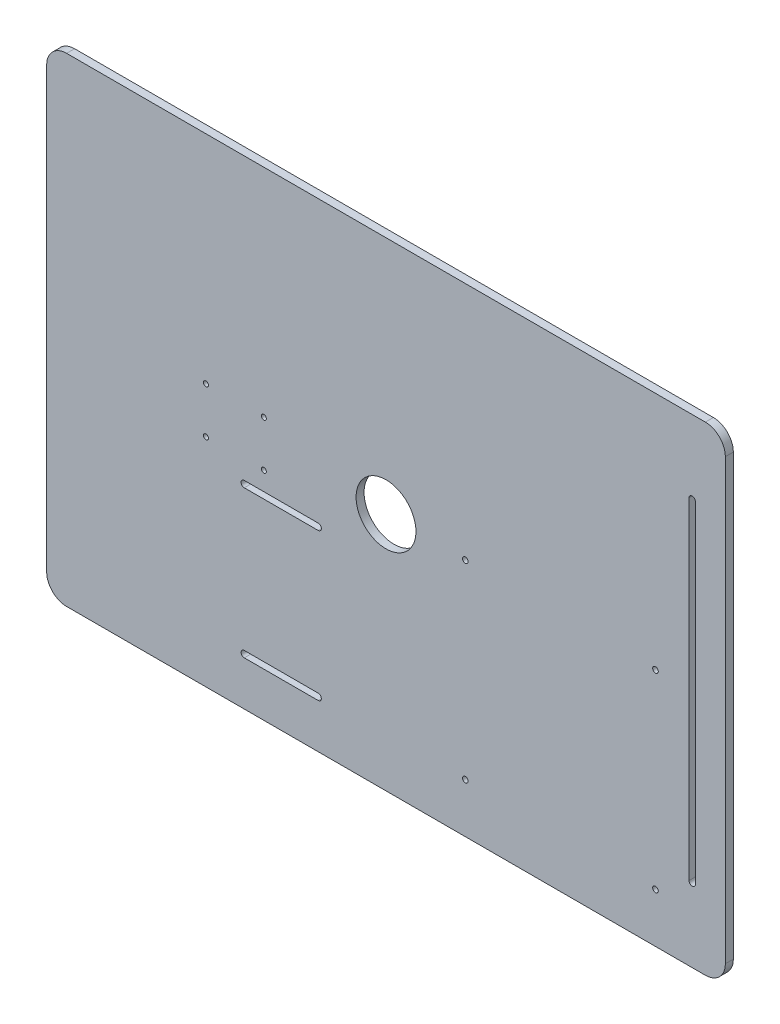
SolidWorks part; units mm, degrees
ref_plane "前视基准面" through (0, 0, 0) normal (0, 0, 1) x (1, 0, 0)
ref_plane "上视基准面" through (0, 0, 0) normal (0, 1, 0) x (1, 0, 0)
ref_plane "右视基准面" through (0, 0, 0) normal (1, 0, 0) x (0, 0, -1)
other "Configuration Table"
sketch "草图1" plane through (0, 0, 0) normal (0, 0, 1) x (1, 0, 0)
  line L0 (-232.03, 0) -> (-100.2513, 0) construction
  line L1 (160, -120) -> (-160, -120)
  line L2 (170, -110) -> (170, 110)
  line L3 (160, 120) -> (-160, 120)
  line L4 (-170, -110) -> (-170, 110)
  line L5 (170, -120) -> (-170, 120) construction
  line L6 (170, 120) -> (-170, -120) construction
  line L7 (0, -161.7122) -> (0, 250.7886) construction
  line L8 (0, 0) -> (270.6764, 0) construction
  line L9 (-110, 120) -> (-110, 83)
  line L10 (-170, 103) -> (-110, 103) construction
  line L11 (-110, 83) -> (-70, 83)
  line L12 (-70, 83) -> (-70, 120)
  line L17 (-100.2513, 0) -> (0, 0) construction
  line L18 (-76.2884, 0) -> (-76.2884, 20.8877) construction
  line L19 (-76.2884, 4.5) -> (-76.2884, -4.5) construction
  line L21 (39.75, 0) -> (135, 0)
  line L23 (151.8, -83) -> (151.8, 83)
  line L26 (155, 83) -> (155, -83)
  line L27 (-98.3572, 27.2299) -> (-98.3572, -46.7701)
  line L28 (98.3491, 27.2299) -> (-150.1076, 27.2299) construction
  line L30 (39.75, 0) -> (39.75, -95.25)
  circle A20 centre (-105, 115) radius 1.75
  circle A21 centre (-75, 115) radius 1.75
  circle A22 centre (-75, 91) radius 1.75
  circle A23 centre (-105, 91) radius 1.75
  circle A24 centre (-105, 115) radius 1.75
  circle A25 centre (-75, 115) radius 1.75
  circle A26 centre (-75, 91) radius 1.75
  circle A27 centre (-105, 91) radius 1.75
  circle A28 centre (-105.7503, -91) radius 1.75
  circle A29 centre (-75.7503, -91) radius 1.75
  circle A30 centre (-75.7503, -115) radius 1.75
  circle A31 centre (-105.7503, -115) radius 1.75
  circle A32 centre (105.7503, -115) radius 1.75
  circle A33 centre (105.7503, -91) radius 1.75
  circle A34 centre (75.7503, -115) radius 1.75
  circle A35 centre (75.7503, -91) radius 1.75
  circle A36 centre (105.7503, 91) radius 1.75
  circle A37 centre (75.7503, 91) radius 1.75
  circle A38 centre (75.7503, 115) radius 1.75
  circle A39 centre (105.7503, 115) radius 1.75
  circle A40 centre (-90.2053, 11.5) radius 1.25
  arc A43 (151.8, 83) -> (155, 83) centre (153.4, 83) cw
  arc A44 (151.8, -83) -> (155, -83) centre (153.4, -83) ccw
  circle A45 centre (0, 0) radius 15
  arc A46 (170, 110) -> (160, 120) centre (160, 110) ccw
  arc A47 (160, -120) -> (170, -110) centre (160, -110) ccw
  circle A48 centre (135, -95.25) radius 1.4
  circle A49 centre (39.75, -95.25) radius 1.4
  circle A50 centre (135, 0) radius 1.4
  circle A51 centre (39.75, 0) radius 1.4
  arc A52 (-160, -120) -> (-170, -110) centre (-160, -110) cw
  arc A53 (-170, 110) -> (-160, 120) centre (-160, 110) cw
  point P0 (0, 0)
  point P52 (-85.7513, 0)
  point P60 (155, 0)
  point P65 (-151.1375, 0)
  point P71 (151.8, 0)
  point P74 (-187.3789, -111.8285)
  point P75 (-135.0334, 0)
  point P76 (-47.7032, -95.25)
  point P77 (0, 0)
  point P78 (-61.0786, -95.25)
  point P89 (-277.0523, -95.25)
  point P90 (-217.0345, -95.25)
  point P91 (-300.3437, -95.25)
  point P92 (-209.514, 0)
  point P93 (-41.0536, 0)
  point P94 (0, 0)
  point P95 (-135.0732, -95.3458)
  point P96 (83.7659, -94.15)
  point P97 (107.2497, -95.25)
  dimension "D5" = 3.5
  dimension "D6" = 3.5
  dimension "D7" = 3.5
  dimension "D15" = 15
  dimension "D18" = 30
  dimension "D19" = 2.5
  dimension "D20" = 2.8
  dimension "D22" = 2.8
  dimension "D23" = 2.8
  dimension "D24" = 2.8
  dimension "D25" = 95.25
  dimension "D28" = 95.25
  dimension "D30" = 35
  dimension "D31" = 10
  dimension "D1" = 240
  dimension "D2" = 340
  dimension "D3" = 60
  dimension "D4" = 37
  dimension "D8" = 40
  dimension "D9" = 5
  dimension "D10" = 5
  dimension "D11" = 5
  dimension "D12" = 5
  dimension "D13" = 60
  dimension "D14" = 3.2
  dimension "D16" = 3.2
  dimension "D17" = 16.6
  dimension "D21" = 74
  dimension "D26" = 95.25
  dimension "D27" = 95.25
  dimension "D29" = 90
extrude "凸台-拉伸1" add sketch "草图1" along normal blind 4 contours L3 A53 L4 A52 L1 A47 L2 A46
extrude "切除-拉伸4" cut sketch "草图1<4>" along normal blind 10 contours A40
sketch "草图1<4>" plane through (0, 0, 0) normal (0, 0, 1) x (1, 0, 0) same geometry as "草图1"
pattern_linear "阵列(线性)1" count 2 spacing 29 along (1, 0, 0) count 2 spacing 23 along (0, -1, 0) of "切除-拉伸4"
extrude "切除-拉伸6" cut sketch "草图1<6>" along normal blind 19 contours L26 A44 L23 A43
sketch "草图1<6>" plane through (0, 0, 0) normal (0, 0, 1) x (1, 0, 0) same geometry as "草图1"
extrude "切除-拉伸8" cut sketch "草图1<7>" along normal blind 9 contours A48 | A49 | A50 | A51
sketch "草图1<7>" plane through (0, 0, 0) normal (0, 0, 1) x (1, 0, 0) same geometry as "草图1"
sketch "草图3" plane through (0, 0, 0) normal (0, 0, 1) x (1, 0, 0)
  line L0 (170, 120) -> (-170, -120) construction
  line L1 (-34, -24) -> (-71, -24)
  line L4 (-34, -20.8) -> (-71, -20.8)
  line L5 (-100.2513, 0) -> (0, 0) construction
  line L6 (-19.6401, -59.2852) -> (-91.4609, -59.2852) construction
  line L7 (-19.6401, -63.7852) -> (-19.6401, -54.7852) construction
  line L8 (-34, -94.5703) -> (-71, -94.5703)
  line L9 (-34, -97.7703) -> (-71, -97.7703)
  arc A0 (-34, -24) -> (-34, -20.8) centre (-34, -22.4) ccw
  arc A1 (-71, -24) -> (-71, -20.8) centre (-71, -22.4) cw
  arc A2 (-71, -94.5703) -> (-71, -97.7703) centre (-71, -96.1703) ccw
  arc A3 (-34, -94.5703) -> (-34, -97.7703) centre (-34, -96.1703) cw
  dimension "D4" = 24
  dimension "D5" = 1.6
  dimension "D6" = 1.6
  dimension "D1" = 37
  dimension "D2" = 3.2
  dimension "D3" = 3.2
  dimension "D7" = 3.2
extrude "切除-拉伸10" cut sketch "草图3" along normal blind 9
extrude "切除-拉伸12" cut sketch "草图1<8>" along normal blind 9 contours A45
sketch "草图1<8>" plane through (0, 0, 0) normal (0, 0, 1) x (1, 0, 0) same geometry as "草图1"
